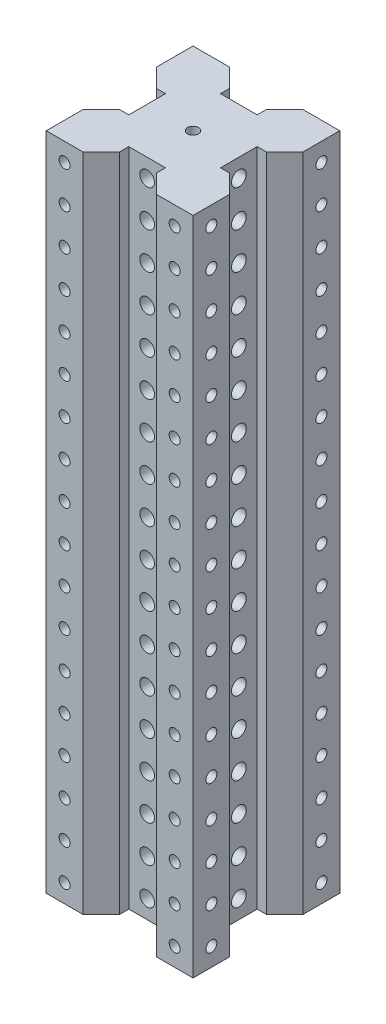
SolidWorks part; units mm, degrees
ref_plane "Front Plane" through (0, 0, 0) normal (0, 0, 1) x (1, 0, 0)
ref_plane "Top Plane" through (0, 0, 0) normal (0, 1, 0) x (1, 0, 0)
ref_plane "Right Plane" through (0, 0, 0) normal (1, 0, 0) x (0, 0, -1)
sketch "Sketch1" plane through (0, 0, 0) normal (0, 0, 1) x (1, 0, 0)
  line L0 (-25.4, 114.3) -> (25.4, -114.3) construction
  line L1 (-25.4, 114.3) -> (25.4, 114.3)
  line L2 (-25.4, 114.3) -> (-25.4, -114.3)
  line L3 (-25.4, -114.3) -> (25.4, -114.3)
  line L4 (25.4, 114.3) -> (25.4, -114.3)
  point P4 (0, 0)
  dimension "D1" = 228.6
  dimension "D2" = 50.8
extrude "Boss-Extrude1" add sketch "Sketch1" along normal blind 50.8
sketch "Sketch2" plane through (0, 0, 50.8) normal (0, 0, 1) x (1, 0, 0)
  line L0 (25.4, 114.3) -> (-25.4, 114.3) construction
  line L1 (-12.7, 241.3) -> (12.7, 241.3)
  line L2 (-12.7, 241.3) -> (-12.7, -241.3)
  line L3 (-12.7, -241.3) -> (12.7, -241.3)
  line L4 (12.7, 241.3) -> (12.7, -241.3)
  line L5 (-25.4, -114.3) -> (25.4, -114.3) construction
  line L6 (0, -27.94) -> (0, 27.94) construction
  line L7 (-25.4, 114.3) -> (-25.4, -114.3) construction
  point P8 (0, 241.3)
  dimension "D1" = 12.7
  dimension "D2" = 127
  dimension "D3" = 127
extrude "Cut-Extrude1" cut sketch "Sketch2" against normal blind 6.35 draft 45
sketch "Sketch3" plane through (0, 0, 44.45) normal (0, 0, 1) x (1, 0, 0)
  line L4 (-6.35, -114.3) -> (6.35, -114.3)
  line L5 (6.35, -114.3) -> (6.35, 114.3)
  line L6 (6.35, 114.3) -> (-6.35, 114.3)
  line L7 (-6.35, 114.3) -> (-6.35, -114.3)
  line L8 (-6.35, -114.3) -> (6.35, -114.3)
  line L9 (6.35, -114.3) -> (6.35, 114.3)
  line L10 (6.35, 114.3) -> (-6.35, 114.3)
  line L11 (-6.35, 114.3) -> (-6.35, -114.3)
  dimension "D1" = 0
extrude "Cut-Extrude2" cut sketch "Sketch3" against normal blind 3.175
hole_wizard "1/4-20 Tapped Hole2" positions "Sketch6" profile "Sketch7" tap size "1/4-20" standard "ANSI Inch"
sketch "Sketch6" plane through (0, 0, 41.275) normal (0, 0, 1) x (1, 0, 0)
  line L0 (6.35, 114.3) -> (-6.35, 114.3) construction
  point P0 (0, 107.95)
  point P90 (0, 0)
  point P92 (0, 0)
  dimension "D1" = 6.35
sketch "Sketch7" plane through (0, 107.95, 41.275) normal (1, 0, 0) x (0, -1, 0)
  line L0 (0, 0) -> (0, 14.2338)
  line L1 (0, 14.2338) -> (2.5527, 12.7)
  line L2 (2.5527, 12.7) -> (2.5527, 0)
  line L5 (2.5527, 0) -> (0, 0)
  line L10 (0, 14.2338) -> (-2.5527, 12.7) construction
  line L11 (0, -6.35) -> (0, 107.95) construction
  dimension "Tap Drill Dia." = 5.1054
  dimension "Tap Drill Depth" = 12.7
  dimension "Drill Angle" = 118
cosmetic thread "Hole Thread2" parameters "D1"=3.048, "D2"=6.35
hole_wizard "#10-24 Tapped Hole2" positions "Sketch8" profile "Sketch9" tap size "#10-24" standard "ANSI Inch"
sketch "Sketch8" plane through (0, 0, 50.8) normal (0, 0, 1) x (1, 0, 0)
  line L0 (-19.05, 114.3) -> (-19.05, 107.95) construction
  line L1 (-12.7, 114.3) -> (-25.4, 114.3) construction
  line L3 (-25.4, -114.3) -> (25.4, -114.3) construction
  line L4 (-25.4, -114.3) -> (25.4, -114.3) construction
  line L6 (19.05, 114.3) -> (19.05, 107.95) construction
  line L7 (25.4, 114.3) -> (12.7, 114.3) construction
  point P0 (-19.05, 107.95)
  point P49 (19.05, 107.95)
  point P62 (20.6973, 104.9085)
  point P63 (0, 0)
  point P66 (19.05, 114.3)
  dimension "D1" = 6.35
sketch "Sketch9" plane through (-19.05, 107.95, 50.8) normal (1, 0, 0) x (0, -1, 0)
  line L0 (0, 0) -> (0, 7.4908)
  line L1 (0, 7.4908) -> (1.8986, 6.35)
  line L2 (1.8986, 6.35) -> (1.8986, 0)
  line L5 (1.8986, 0) -> (0, 0)
  line L10 (0, 7.4908) -> (-1.8987, 6.35) construction
  line L11 (0, -6.35) -> (0, 107.95) construction
  dimension "Tap Drill Dia." = 3.7973
  dimension "Tap Drill Depth" = 6.35
  dimension "Drill Angle" = 118
cosmetic thread "Hole Thread29" parameters "D1"=3.048, "D2"=4.826
cosmetic thread "Hole Thread56" parameters "D1"=3.048, "D2"=4.826
hole_wizard "#10-24 Tapped Hole1" positions "Sketch4" profile "Sketch5" tap size "#10-24" standard "ANSI Inch"
sketch "Sketch4" plane through (0, 114.3, 0) normal (0, 1, 0) x (1, 0, 0)
  line L0 (-25.4, 0) -> (25.4, -50.8) construction
  point P0 (0, -25.4)
  point P10 (0, -25.4)
cosmetic thread "Hole Thread1" parameters "D1"=3.048, "D2"=4.826
sketch "Sketch5" plane through (0, 114.3, 25.4) normal (1, 0, 0) x (0, 0, 1)
  line L0 (0, 0) -> (0, 26.5408)
  line L1 (0, 26.5408) -> (1.8986, 25.4)
  line L2 (1.8986, 25.4) -> (1.8986, 0)
  line L5 (1.8986, 0) -> (0, 0)
  line L10 (0, 26.5408) -> (-1.8987, 25.4) construction
  line L11 (0, -6.35) -> (0, 107.95) construction
  dimension "Tap Drill Dia." = 3.7973
  dimension "Tap Drill Depth" = 25.4
  dimension "Drill Angle" = 118
pattern_linear "LPattern1" count 18 spacing 12.7 along (0, -1, 0) of "#10-24 Tapped Hole2", "1/4-20 Tapped Hole2"
pattern_circular "CirPattern1" count 4 over 360 of "Cut-Extrude1", "Cut-Extrude2", "1/4-20 Tapped Hole2", "#10-24 Tapped Hole2", "LPattern1"
